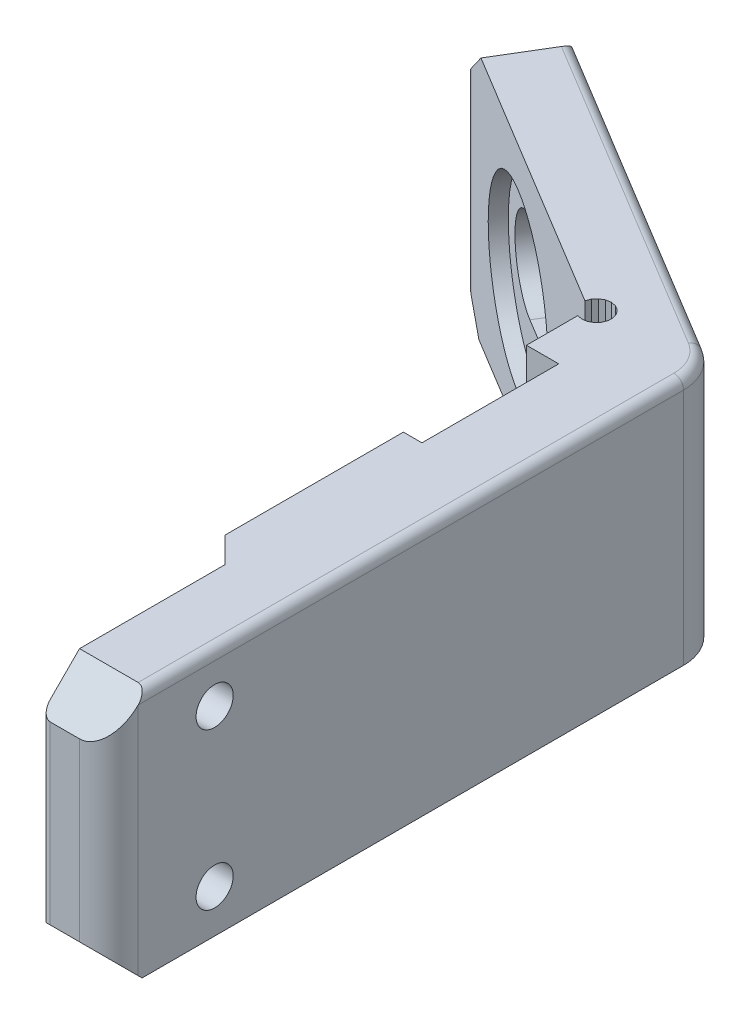
SolidWorks part; units mm, degrees
ref_plane "Front Plane" through (0, 0, 0) normal (0, 0, 1) x (1, 0, 0)
ref_plane "Top Plane" through (0, 0, 0) normal (0, 1, 0) x (1, 0, 0)
ref_plane "Right Plane" through (0, 0, 0) normal (1, 0, 0) x (0, 0, -1)
ref_plane "PY -20.700" through (0, -20.7, 0) normal (0, 1, 0) x (1, 0, 0)
sketch "leg and pad sketch" plane through (0, -20.7, 0) normal (0, 1, 0) x (1, 0, 0)
  line L0 (-0.5513, 30.3327) -> (-0.3673, 30.8194)
  line L1 (-0.3673, 30.8194) -> (-0.028, 31.2139)
  line L2 (-0.028, 31.2139) -> (0.4256, 31.4688)
  line L3 (0.4256, 31.4688) -> (0.939, 31.5534)
  line L4 (0.939, 31.5534) -> (1.4504, 31.4576)
  line L5 (1.4504, 31.4576) -> (1.8983, 31.1928)
  line L6 (1.8983, 31.1928) -> (2.2288, 30.7909)
  line L7 (2.2288, 30.7909) -> (2.4021, 30.3003)
  line L8 (2.4021, 30.3003) -> (2.3973, 29.78)
  line L9 (2.3973, 29.78) -> (2.2152, 29.2926)
  line L10 (2.2152, 29.2926) -> (1.8775, 28.8968)
  line L11 (1.8775, 28.8968) -> (1.4248, 28.6402)
  line L12 (1.4248, 28.6402) -> (0.9118, 28.5536)
  line L13 (0.9118, 28.5536) -> (0.4, 28.6475)
  line L14 (0.4, 28.6475) -> (0.4, -7.48)
  line L15 (0.4, -7.48) -> (4.42, -11.5)
  line L16 (4.42, -11.5) -> (4.42, -30.37)
  line L17 (4.42, -30.37) -> (11.42, -30.37)
  line L18 (11.42, -30.37) -> (11.42, 31.2838)
  line L19 (11.42, 31.2838) -> (-27.2048, 54.5947)
  line L20 (-27.2048, 54.5947) -> (-30.8218, 48.6015)
  line L21 (-30.8218, 48.6015) -> (-0.5513, 30.3327)
extrude "leg and pad" add sketch "leg and pad sketch" along normal mid plane 26
ref_plane "PX 1.350" through (1.35, 0, 0) normal (1, 0, 0) x (0, 0, -1)
sketch "screw head relief sketch" plane through (1.35, 0, 0) normal (1, 0, 0) x (0, 0, -1)
  line L0 (23.4, -12.7) -> (23.4, -6.7)
  line L1 (23.4, -6.7) -> (9.4, -6.7)
  line L2 (9.4, -6.7) -> (9.4, -12.7)
  line L3 (9.4, -12.7) -> (23.4, -12.7)
extrude "screw head relief" cut sketch "screw head relief sketch" against normal mid plane 4.7
sketch "lens frame relief, side sketch" plane through (0, -20.7, 0) normal (0, 1, 0) x (1, 0, 0)
  line L0 (-1, 15) -> (1.8, 15)
  line L1 (1.8, 15) -> (1.8, -8.88)
  line L2 (1.8, -8.88) -> (-1, -8.88)
  line L3 (-1, -8.88) -> (-1, 15)
extrude "lens frame relief, side" cut sketch "lens frame relief, side sketch" against normal mid plane 28
sketch "insert flange relief sketch" plane through (0, -20.7, 0) normal (0, 1, 0) x (1, 0, 0)
  line L0 (-18.3249, 39.8914) -> (-17.0331, 42.0318)
  line L1 (-17.0331, 42.0318) -> (-9.3276, 37.3814)
  line L2 (-9.3276, 37.3814) -> (-10.6194, 35.241)
  line L3 (-10.6194, 35.241) -> (-18.3249, 39.8914)
revolve "insert flange relief" cut sketch "insert flange relief sketch" angle 360 about L0
sketch "M6 slot end 1 sketch" plane through (0, -20.7, 0) normal (0, 1, 0) x (1, 0, 0)
  line L0 (-20.4653, 41.1832) -> (-15.8149, 48.8886)
  line L1 (-15.8149, 48.8886) -> (-11.9621, 46.5634)
  line L2 (-11.9621, 46.5634) -> (-16.6125, 38.858)
  line L3 (-16.6125, 38.858) -> (-20.4653, 41.1832)
revolve "M6 slot end 1" cut sketch "M6 slot end 1 sketch" angle 360 about L0
sketch "M6 slot end 2 sketch" plane through (0, -20.7, 0) normal (0, 1, 0) x (1, 0, 0)
  line L0 (-16.1845, 38.5996) -> (-11.5341, 46.3051)
  line L1 (-11.5341, 46.3051) -> (-7.6813, 43.9799)
  line L2 (-7.6813, 43.9799) -> (-12.3317, 36.2744)
  line L3 (-12.3317, 36.2744) -> (-16.1845, 38.5996)
revolve "M6 slot end 2" cut sketch "M6 slot end 2 sketch" angle 360 about L0
sketch "M6 slot middle sketch" plane through (0, -20.7, 0) normal (0, 1, 0) x (1, 0, 0)
  line L0 (-16.1845, 38.5996) -> (-20.4653, 41.1832)
  line L1 (-20.4653, 41.1832) -> (-15.8149, 48.8886)
  line L2 (-15.8149, 48.8886) -> (-11.5341, 46.3051)
  line L3 (-11.5341, 46.3051) -> (-16.1845, 38.5996)
extrude "M6 slot middle" cut sketch "M6 slot middle sketch" against normal mid plane 9
ref_plane "PX 7.920" through (7.92, 0, 0) normal (1, 0, 0) x (0, 0, -1)
sketch "screw holes sketch" plane through (7.92, 0, 0) normal (1, 0, 0) x (0, 0, -1)
  circle A0 centre (-19.54, -28.7) radius 1.9
  circle A1 centre (-19.54, -12.7) radius 1.9
extrude "screw holes" cut sketch "screw holes sketch" against normal mid plane 9
chamfer "leg top corners" distance 4 angle 45 2 edges at (7.92, -7.7, 30.37) (7.92, -33.7, 30.37) tangent propagation no
chamfer "pad end corners" distance 4 angle 45 2 edges at (-29.0133, -7.7, -51.5981) (-29.0133, -33.7, -51.5981) tangent propagation no
fillet "outside of the bend" radius 5 1 edges at (11.42, -20.7, -31.2838) tangent propagation no
fillet "leg top outer edge" radius 3 1 edges at (11.42, -20.7, 30.37) tangent propagation no
fillet "pad end outer edge" radius 3 1 edges at (-27.2048, -20.7, -54.5947) tangent propagation no
fillet "leg top inner edge" radius 1 1 edges at (4.42, -20.7, 30.37) tangent propagation no
fillet "pad end inner edge" radius 1 1 edges at (-30.8218, -20.7, -48.6015) tangent propagation no
chamfer "bed face chamfer" distance 0.6 angle 45 7 edges at (-13.9742, -33.7, -38.4337) (-7.3883, -33.7, -42.635) (4.42, -33.7, 18.935) (1.8, -33.7, -3.06) (0.4, -33.7, -21.8237) (10.7742, -33.7, -30.9193) (11.42, -33.7, -1.0457)
fillet "top face edge" radius 1 3 edges at (-7.3883, -7.7, -42.635) (10.7742, -7.7, -30.9193) (11.42, -7.7, -1.0457)
equation "\"diffL\"= 608.8mm"
equation "\"diffW\"= 329.4mm"
equation "\"diffT\"= 2.9mm"
equation "\"chanSlotW\"= 12.9mm"
equation "\"chanSlotDepth\"= 11.13mm"
equation "\"chanFloor\"= 1.57mm"
equation "\"chanLeg\"= 12.7mm"
equation "\"lightL\"= 605mm"
equation "\"lightW\"= 331mm"
equation "\"lightH\"= 92mm"
equation "\"lightSideFlat\"= 30mm"
equation "\"lightSlopeLen\"= 33.1mm"
equation "\"lightWingDepth\"= 47.9mm"
equation "\"lightWingFlat\"= 90.2mm"
equation "\"lightChanW\"= 99.6mm"
equation "\"lightChanStand\"= 44.1mm"
equation "\"insFlangeD\"= 12.3mm"
equation "\"insFromEnd\"= 20.7mm"
equation "\"insUpSlope\"= 20.8mm"
equation "\"gaugeH\"= 10mm"
equation "\"gaugeStepLen\"= 14mm"
equation "\"gaugeStepW0\"= 13.1mm"
equation "\"gaugeStepDW\"= 0.2mm"
equation "\"gaugeSteps\"= 5mm"
equation "\"gaugeHandleLen\"= 30mm"
equation "\"gaugeHandleW\"= 24mm"
equation "\"gaugeSlot0\"= 3mm"
equation "\"gaugeSlotD\"= 0.1mm"
equation "\"gaugeSlotDepth\"= 8mm"
equation "\"gap\"= 25.4mm"
equation "\"edgeL\"= 1mm"
equation "\"edgeW\"= 0.75mm"
equation "\"proud\"= 1.5mm"
equation "\"seatClr\"= 0.15mm"
equation "\"tongueClrZ\"= 0.1mm"
equation "\"tongueClrX\"= 0.25mm"
equation "\"tongueLen\"= 30mm"
equation "\"armSide\"= 45mm"
equation "\"armEnd\"= 20mm"
equation "\"cornerCham\"= 3mm"
equation "\"brkW\"= 26mm"
equation "\"brkT\"= 7mm"
equation "\"brkSeatClr\"= 0.2mm"
equation "\"brkScrewSpan\"= 16mm"
equation "\"pilotD\"= 2.7mm"
equation "\"pilotDepth\"= 10mm"
equation "\"screwClrD\"= 3.9mm"
equation "\"jogBelow\"= 4mm"
equation "\"padT\"= 7mm"
equation "\"padLen\"= 31mm"
equation "\"m6Clr\"= 7mm"
equation "\"m6Slot\"= 3mm"
equation "\"flangeRelD\"= 17mm"
equation "\"flangeRelDepth\"= 1.5mm"
equation "\"relLen\"= 7mm"
equation "\"relDepth\"= 4mm"
equation "\"relLand\"= 2mm"
equation "\"knockN\"= 100mm"
equation "\"petgcfE\"= 3000mm"
equation "\"mockExtent\"= 110mm"
equation "\"relZnear\"= 9.4mm"
equation "\"relZfar\"= 23.4mm"
equation "\"headD\"= 8mm"
equation "\"headH\"= 2.5mm"
equation "\"headFromEnd\"= 6.8mm"
equation "\"headBack\"= 16.4mm"
equation "\"sideClr\"= 0.4mm"
equation "\"cornerRelR\"= 1.5mm"
equation "\"cornerRelBack\"= 0.6mm"
equation "\"endHeadH\"= 2.8mm"
equation "\"footClr\"= 1.2mm"
equation "\"footEndClr\"= 3.5mm"
equation "\"footLift\"= 6mm"
equation "\"footBlockClr\"= 0.5mm"
equation "\"footBack\"= 50mm"
equation "\"footFwd\"= 10mm"
equation "\"footBraceEnd\"= 3mm"
equation "\"footLoadN\"= 25mm"
equation "\"spacerLen\"= 60mm"
equation "\"spacerShort\"= 0.5mm"
equation "\"spacerCham\"= 0.8mm"
equation "\"spacerPerSide\"= 3mm"
equation "\"spacerPerEnd\"= 1mm"
equation "\"toolR\"= 9mm"
equation "\"visR\"= 4mm"
equation "\"edgeR\"= 1mm"
equation "\"bendOutR\"= 5mm"
equation "\"insideR\"= 2.5mm"
equation "\"footCornerR\"= 10mm"
equation "\"footFrontR\"= 8mm"
equation "\"braceKinkR\"= 12mm"
equation "\"bedCham\"= 1mm"
equation "\"bedChamSmall\"= 0.6mm"
equation "\"soleTopR\"= 2mm"
equation "\"cornerR\"= 6mm"
equation "\"rimInR\"= 1mm"
equation "\"insFlangeH\"= 1mm"
equation "\"insHoleFinishD\"= 4.5mm"
equation "\"insLen\"= 6.4mm"
equation "\"footToeTip\"= 4mm"
equation "\"cgInset\"= 4mm"
equation "\"lampWeightN\"= 51mm"
equation "\"frameWeightN\"= 10mm"
equation "\"bumpIn\"= 8mm"
equation "\"bumpH\"= 3mm"
equation "\"legBelowFront\"= 2mm"
equation "\"lipClr\"= 0.1mm"
equation "\"revealR\"= 2mm"
equation "\"frontCham\"= 1mm"
equation "\"leanDeg\" = 5mm"
equation "\"footTailT\" = 6mm"
equation "\"v1LeanDeg\" = 4.5mm"
equation "\"toeNoseR\" = 5mm"
equation "\"petgE\" = 2000mm"
equation "\"cheekT\" = 8mm"
equation "\"handleUp\" = 50mm"
equation "\"handleZ\" = -10mm"
equation "\"gripD\" = 19.05mm"
equation "\"gripClr\" = 0.5mm"
equation "\"bossWall\" = 5mm"
equation "\"bossLen\" = 14mm"
equation "\"socketFloor\" = 4mm"
equation "\"barEndClr\" = 1mm"
equation "\"lipH\" = 4mm"
equation "\"lipDeep\" = 6mm"
equation "\"stripT\" = 1.3mm"
equation "\"stripW\" = 12mm"
equation "\"stripClr\" = 0.5mm"
equation "\"stripBack\" = 3mm"
equation "\"endRelClr\" = 1mm"
equation "\"cornerScrewX\" = 5.5mm"
equation "\"cornerScrewZ\" = 6mm"
equation "\"cornerScrewD\" = 8.5mm"
equation "\"footTabIn\" = 33mm"
equation "\"footTabZ1\" = 50mm"
equation "\"footTabZ2\" = 19mm"
equation "\"footTabR\" = 8mm"
equation "\"landAx0\" = -17mm"
equation "\"landAz0\" = -30mm"
equation "\"landAx1\" = -3mm"
equation "\"landAz1\" = -18mm"
equation "\"landBx0\" = -60mm"
equation "\"landBz0\" = -43mm"
equation "\"landBx1\" = -46mm"
equation "\"landBz1\" = -27mm"
